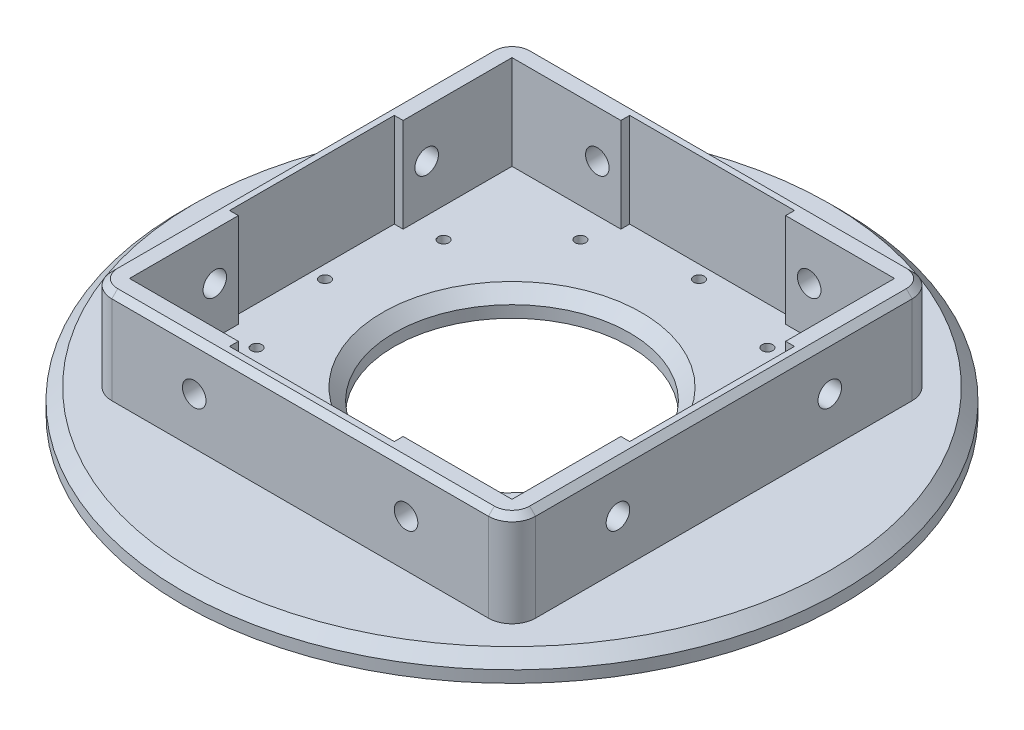
SolidWorks part; units mm, degrees
ref_plane "Front Plane" through (0, 0, 0) normal (0, 0, 1) x (1, 0, 0)
ref_plane "Top Plane" through (0, 0, 0) normal (0, 1, 0) x (1, 0, 0)
ref_plane "Right Plane" through (0, 0, 0) normal (1, 0, 0) x (0, 0, -1)
sketch "Sketch1" plane through (0, 0, 0) normal (0, 1, 0) x (1, 0, 0)
  line L0 (-57.15, 57.15) -> (57.15, 57.15)
  line L1 (-22.225, -53.975) -> (22.225, -53.975)
  line L2 (-53.975, -22.225) -> (-53.975, 22.225)
  line L3 (-22.225, 53.975) -> (22.225, 53.975)
  line L4 (53.975, -22.225) -> (53.975, 22.225)
  line L5 (-53.975, -53.975) -> (53.975, 53.975) construction
  line L6 (-53.975, 53.975) -> (53.975, -53.975) construction
  line L7 (57.15, -57.15) -> (57.15, 57.15)
  line L8 (-57.15, -57.15) -> (57.15, -57.15)
  line L9 (-57.15, -57.15) -> (-57.15, 57.15)
  line L10 (-22.225, 53.975) -> (-22.225, 51.5938)
  line L11 (-51.5937, -51.5938) -> (-22.225, -51.5938)
  line L12 (-51.5937, -51.5938) -> (-51.5938, -22.225)
  line L13 (-51.5937, 51.5938) -> (-22.225, 51.5938)
  line L14 (51.5938, -51.5938) -> (51.5937, -22.225)
  line L15 (-51.5937, -51.5938) -> (51.5938, 51.5938) construction
  line L16 (-51.5937, 51.5938) -> (51.5938, -51.5938) construction
  line L17 (-53.975, 22.225) -> (-51.5938, 22.225)
  line L18 (22.225, 53.975) -> (22.225, 51.5938)
  line L19 (53.975, 22.225) -> (51.5937, 22.225)
  line L20 (-53.975, -22.225) -> (-51.5938, -22.225)
  line L21 (-22.225, -53.975) -> (-22.225, -51.5938)
  line L22 (22.225, -53.975) -> (22.225, -51.5938)
  line L23 (53.975, -22.225) -> (51.5937, -22.225)
  line L24 (-51.5938, 22.225) -> (-51.5937, 51.5938)
  line L25 (-53.975, 53.975) -> (53.975, 53.975) construction
  line L26 (-53.975, -53.975) -> (-53.975, 53.975) construction
  line L27 (22.225, -51.5938) -> (51.5938, -51.5938)
  line L28 (53.975, -53.975) -> (53.975, 53.975) construction
  line L29 (51.5937, 22.225) -> (51.5938, 51.5938)
  line L30 (22.225, 51.5938) -> (51.5938, 51.5938)
  line L31 (-53.975, -53.975) -> (53.975, -53.975) construction
  circle A0 centre (0, 0) radius 88.9
  circle A1 centre (0, 0) radius 50.4444 construction
  circle A2 centre (0, 50.4444) radius 1.4351
  circle A14 centre (0, 0) radius 31.75
  circle A15 centre (25.2222, 43.6861) radius 1.4351
  circle A16 centre (43.6861, 25.2222) radius 1.4351
  circle A17 centre (50.4444, 0) radius 1.4351
  circle A18 centre (43.6861, -25.2222) radius 1.4351
  circle A19 centre (25.2222, -43.6861) radius 1.4351
  circle A20 centre (0, -50.4444) radius 1.4351
  circle A21 centre (-25.2222, -43.6861) radius 1.4351
  circle A22 centre (-43.6861, -25.2222) radius 1.4351
  circle A23 centre (-50.4444, 0) radius 1.4351
  circle A24 centre (-43.6861, 25.2222) radius 1.4351
  circle A25 centre (-25.2222, 43.6861) radius 1.4351
  point P30 (10.7306, 18.5859)
  point P58 (-53.975, 0)
  point P59 (53.975, 0)
  point P60 (0, 53.975)
  point P61 (0, -53.975)
  point P64 (0, 0)
  dimension "D1" = 177.8
  dimension "D2" = 2.8702
  dimension "D3" = 100.8888
  dimension "D9" = 63.5
  dimension "D5" = 107.95
  dimension "D6" = 107.95
  dimension "D8" = 103.1875
  dimension "D10" = 44.45
  dimension "D11" = 44.45
  dimension "D12" = 103.1875
  dimension "D7" = 3.175
  dimension "D4" = 12
extrude "Boss-Extrude1" add sketch "Sketch1" along normal blind 6.35 contours A0 L8 L9 L0 L7 | L30 L18 L3 L10 L13 L24 L17 L2 L20 L12 L11 L21 L1 L22 L27 L14 L23 L4 L19 L29 A14 A24 A23 A22 A21 A20 A19 A18 A17 A16 A15 A2 region at (-20.6984, 0, 52.7844) region at (-86.3855, 0, 0)
extrude "Boss-Extrude2" add sketch "Sketch1<3>" along normal blind 31.75 contours L9 L8 L7 L0 L18 L30 L29 L19 L4 L23 L14 L27 L22 L1 L21 L11 L12 L20 L2 L17 L24 L13 L10 L3 region at (0, 0, -55.5336)
sketch "Sketch1<3>" plane through (0, 0, 0) normal (0, 1, 0) x (1, 0, 0) same geometry as "Sketch1"
sketch "Sketch3" plane through (0, 0, 0) normal (0, 0, 1) x (1, 0, 0)
  line L0 (0, 31.75) -> (0, 6.35) construction
  line L1 (-57.15, 19.05) -> (57.15, 19.05) construction
  line L4 (-57.15, 6.35) -> (57.15, 6.35)
  line L5 (57.15, 6.35) -> (57.15, 31.75)
  line L6 (57.15, 31.75) -> (-57.15, 31.75)
  line L7 (-57.15, 31.75) -> (-57.15, 6.35)
  line L8 (-57.15, 6.35) -> (57.15, 6.35) construction
  line L9 (57.15, 6.35) -> (57.15, 31.75) construction
  line L10 (57.15, 31.75) -> (-57.15, 31.75) construction
  line L11 (-57.15, 31.75) -> (-57.15, 6.35) construction
  circle A0 centre (-28.575, 19.05) radius 3.175
  circle A1 centre (28.575, 19.05) radius 3.175
  point P9 (0, 19.05)
  dimension "D2" = 28.575
  dimension "D4" = 6.35
  dimension "D3" = 28.575
  dimension "D1" = 0
extrude "Cut-Extrude1" cut sketch "Sketch3" against normal through all and the other way through all contours L1 A0 | A0 | A1 region at (-28.575, 19.05, 0)
sketch "Sketch4" plane through (0, 0, 0) normal (1, 0, 0) x (0, 0, -1)
  line L0 (0, 31.75) -> (0, 6.35) construction
  line L1 (-57.15, 19.05) -> (57.15, 19.05) construction
  line L2 (-57.15, 6.35) -> (57.15, 6.35) construction
  line L3 (57.15, 6.35) -> (57.15, 31.75) construction
  line L4 (57.15, 31.75) -> (-57.15, 31.75) construction
  line L5 (-57.15, 31.75) -> (-57.15, 6.35) construction
  line L6 (-57.15, 31.75) -> (57.15, 31.75) construction
  circle A0 centre (-28.575, 19.05) radius 3.175
  circle A1 centre (28.575, 19.05) radius 3.175
  point P9 (0, 19.05)
  point P13 (0, 31.75)
  dimension "D3" = 6.35
  dimension "D1" = 28.575
  dimension "D2" = 28.575
extrude "Cut-Extrude2" cut sketch "Sketch4" against normal through all both and the other way through all
fillet "Fillet1" radius 6.35 4 edges at (-57.15, 19.05, 57.15) (-57.15, 19.05, -57.15) (57.15, 19.05, -57.15) (57.15, 19.05, 57.15)
chamfer "Chamfer1" distance 3.175 angle 45 2 edges at (0, 6.35, 88.9) (0, 6.35, 31.75)
chamfer "Chamfer2" distance 1.5875 angle 45 8 edges at (0, 31.75, -57.15) (-55.2901, 31.75, -55.2901) (55.2901, 31.75, -55.2901) (-57.15, 31.75, 0) (57.15, 31.75, 0) (-55.2901, 31.75, 55.2901) (55.2901, 31.75, 55.2901) (0, 31.75, 57.15)
